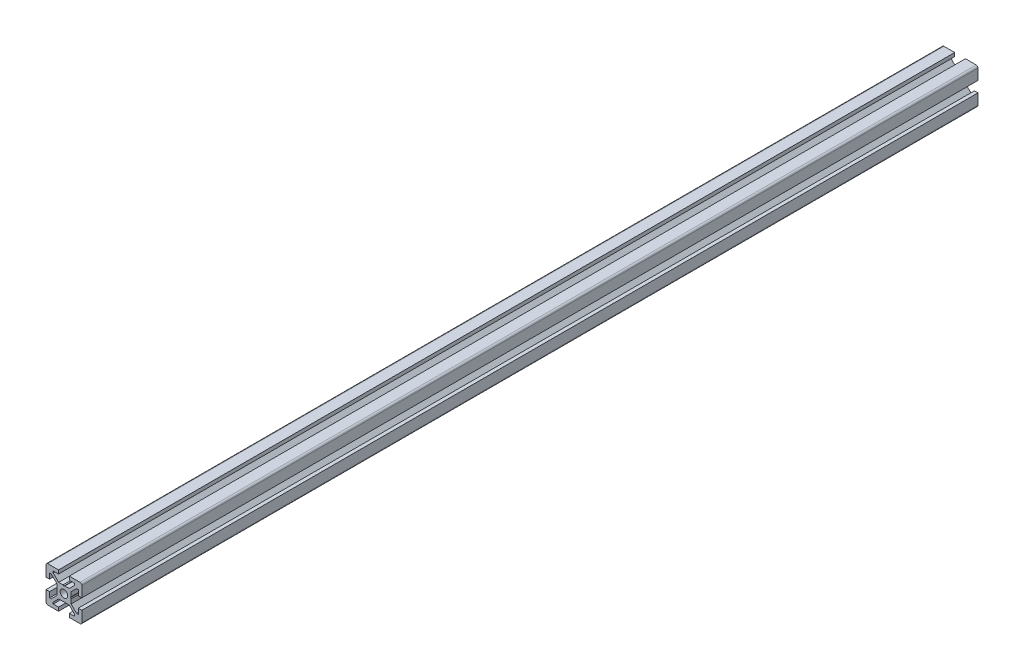
SolidWorks part; units mm, degrees
ref_plane "Front Plane" through (0, 0, 0) normal (0, 0, 1) x (1, 0, 0)
ref_plane "Top Plane" through (0, 0, 0) normal (0, 1, 0) x (1, 0, 0)
ref_plane "Right Plane" through (0, 0, 0) normal (1, 0, 0) x (0, 0, -1)
ref_plane "Plane1" through (0, 0, 0) normal (0, 0, 1) x (1, 0, 0)
sketch "Sketch1" plane through (0, 0, 0) normal (0, 0, 1) x (1, 0, 0)
  line L0 (-10, -3) -> (-10, -9)
  line L1 (-9, -10) -> (-3, -10)
  line L2 (-3, -10) -> (-3, -8)
  line L3 (-3, -8) -> (-6, -8)
  line L4 (-6, -8) -> (-6, -7.0607)
  line L5 (-6, -7.0607) -> (-2.9393, -4)
  line L6 (-2.9393, -4) -> (-0.5196, -4)
  line L7 (-0.5196, -4) -> (0, -3.7)
  line L8 (0, -3.7) -> (0.5196, -4)
  line L9 (0.5196, -4) -> (2.9393, -4)
  line L10 (2.9393, -4) -> (6, -7.0607)
  line L11 (6, -7.0607) -> (6, -8)
  line L12 (6, -8) -> (3, -8)
  line L13 (3, -8) -> (3, -10)
  line L14 (3, -10) -> (9, -10)
  line L15 (10, -9) -> (10, -3)
  line L16 (10, -3) -> (8, -3)
  line L17 (8, -3) -> (8, -6)
  line L18 (8, -6) -> (7.0607, -6)
  line L19 (7.0607, -6) -> (4, -2.9393)
  line L20 (4, -2.9393) -> (4, -0.5196)
  line L21 (4, -0.5196) -> (3.7, 0)
  line L22 (3.7, 0) -> (4, 0.5196)
  line L23 (4, 0.5196) -> (4, 2.9393)
  line L24 (4, 2.9393) -> (7.0607, 6)
  line L25 (7.0607, 6) -> (8, 6)
  line L26 (8, 6) -> (8, 3)
  line L27 (8, 3) -> (10, 3)
  line L28 (10, 3) -> (10, 9)
  line L29 (9, 10) -> (3, 10)
  line L30 (3, 10) -> (3, 8)
  line L31 (3, 8) -> (6, 8)
  line L32 (6, 8) -> (6, 7.0607)
  line L33 (6, 7.0607) -> (2.9393, 4)
  line L34 (2.9393, 4) -> (0.5196, 4)
  line L35 (0.5196, 4) -> (0, 3.7)
  line L36 (0, 3.7) -> (-0.5196, 4)
  line L37 (-0.5196, 4) -> (-2.9393, 4)
  line L38 (-2.9393, 4) -> (-6, 7.0607)
  line L39 (-6, 7.0607) -> (-6, 8)
  line L40 (-6, 8) -> (-3, 8)
  line L41 (-3, 8) -> (-3, 10)
  line L42 (-3, 10) -> (-9, 10)
  line L43 (-10, 9) -> (-10, 3)
  line L44 (-10, 3) -> (-8, 3)
  line L45 (-8, 3) -> (-8, 6)
  line L46 (-8, 6) -> (-7.0607, 6)
  line L47 (-7.0607, 6) -> (-4, 2.9393)
  line L48 (-4, 2.9393) -> (-4, 0.5196)
  line L49 (-4, 0.5196) -> (-3.7, 0)
  line L50 (-3.7, 0) -> (-4, -0.5196)
  line L51 (-4, -0.5196) -> (-4, -2.9393)
  line L52 (-4, -2.9393) -> (-7.0607, -6)
  line L53 (-7.0607, -6) -> (-8, -6)
  line L54 (-8, -6) -> (-8, -3)
  line L55 (-8, -3) -> (-10, -3)
  arc A0 (-10, -9) -> (-9, -10) centre (-9, -9) ccw
  arc A1 (9, -10) -> (10, -9) centre (9, -9) ccw
  arc A2 (10, 9) -> (9, 10) centre (9, 9) ccw
  arc A3 (-9, 10) -> (-10, 9) centre (-9, 9) ccw
extrude "Boss-Extrude1" add sketch "Sketch1" against normal blind 500
ref_plane "Plane2" through (0, 0, 0) normal (1, 0, 0) x (0, 0, -1)
sketch "Sketch2" plane through (0, 0, 0) normal (1, 0, 0) x (0, 0, -1)
  line L0 (0, 0) -> (0, 2.1)
  line L1 (0, 2.1) -> (500, 2.1)
  line L2 (500, 2.1) -> (500, 0)
  line L3 (500, 0) -> (0, 0)
  line L4 (500, 0) -> (0, 0) construction
revolve "Cut-Revolve1" cut sketch "Sketch2" angle 360 about L4 reverse direction yes
